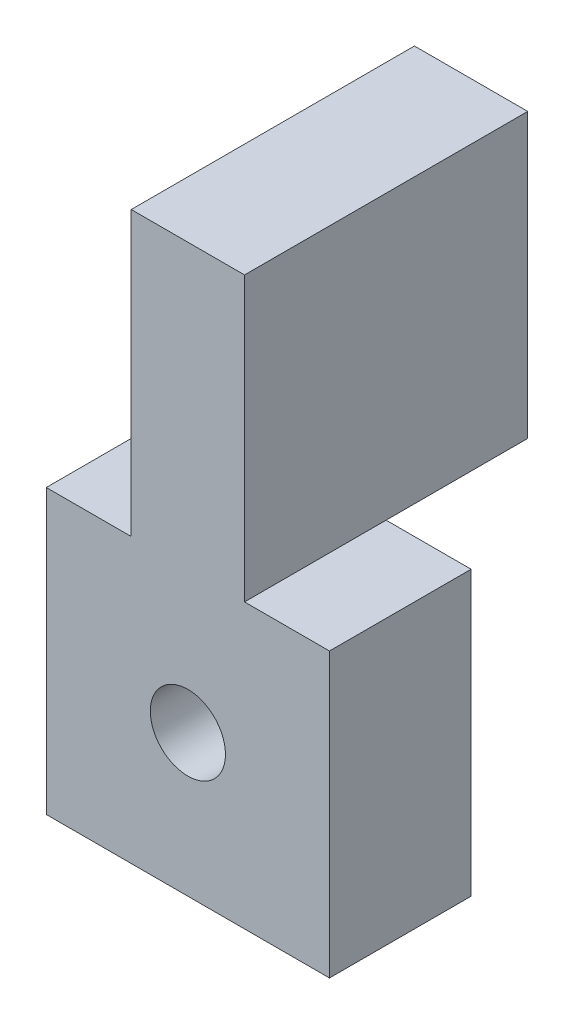
SolidWorks part; units mm, degrees
ref_plane "Front Plane" through (0, 0, 0) normal (0, 0, 1) x (1, 0, 0)
ref_plane "Top Plane" through (0, 0, 0) normal (0, 1, 0) x (1, 0, 0)
ref_plane "Right Plane" through (0, 0, 0) normal (1, 0, 0) x (0, 0, -1)
sketch "Sketch1" plane through (0, 0, 0) normal (0, 0, 1) x (1, 0, 0)
  line L1 (-10, 10) -> (10, 10)
  line L2 (-10, 10) -> (-10, -10)
  line L3 (-10, -10) -> (10, -10)
  line L4 (10, 10) -> (10, -10)
  line L5 (-10, 10) -> (10, -10) construction
  line L6 (-10, -10) -> (10, 10) construction
  line L7 (-4, 30) -> (4, 30)
  line L8 (-4, 30) -> (-4, 10)
  line L9 (-4, 10) -> (4, 10)
  line L10 (4, 30) -> (4, 10)
  line L11 (-4, 30) -> (4, 10) construction
  line L12 (-4, 10) -> (4, 30) construction
  point P0 (0, 0)
  point P6 (0, 20)
  point P11 (0, 0)
  dimension "D1" = 20
  dimension "D2" = 20
  dimension "D3" = 8
  dimension "D4" = 20
extrude "Boss-Extrude1" add sketch "Sketch1" along normal blind 10 contours L4 L1 L2 L3 | L10 L7 L8 L1 region at (0, 0, 0) region at (0, 20, 0)
hole_wizard "#4 (0.209) Diameter Hole1" positions "Sketch2" profile "Sketch3" hole size "#4" standard "ANSI Inch" end condition through all
sketch "Sketch2" plane through (0, 0, 10) normal (0, 0, 1) x (1, 0, 0)
  point P0 (0, 0)
sketch "Sketch3" plane through (0, 0, 10) normal (1, 0, 0) x (0, -1, 0)
  line L0 (0, 0) -> (0, 10)
  line L1 (0, 10) -> (2.6543, 10)
  line L2 (2.6543, 10) -> (2.6543, 0)
  line L5 (2.6543, 0) -> (0, 0)
  line L11 (0, -6.35) -> (0, 107.95) construction
  dimension "Thru Hole Dia." = 5.3086
  dimension "Thru Hole Depth" = 10
extrude "Boss-Extrude2" add sketch "Sketch1<3>" against normal blind 10 contours L10 L7 L8 L1 region at (0, 20, 0)
sketch "Sketch1<3>" plane through (0, 0, 0) normal (0, 0, 1) x (1, 0, 0) same geometry as "Sketch1"
